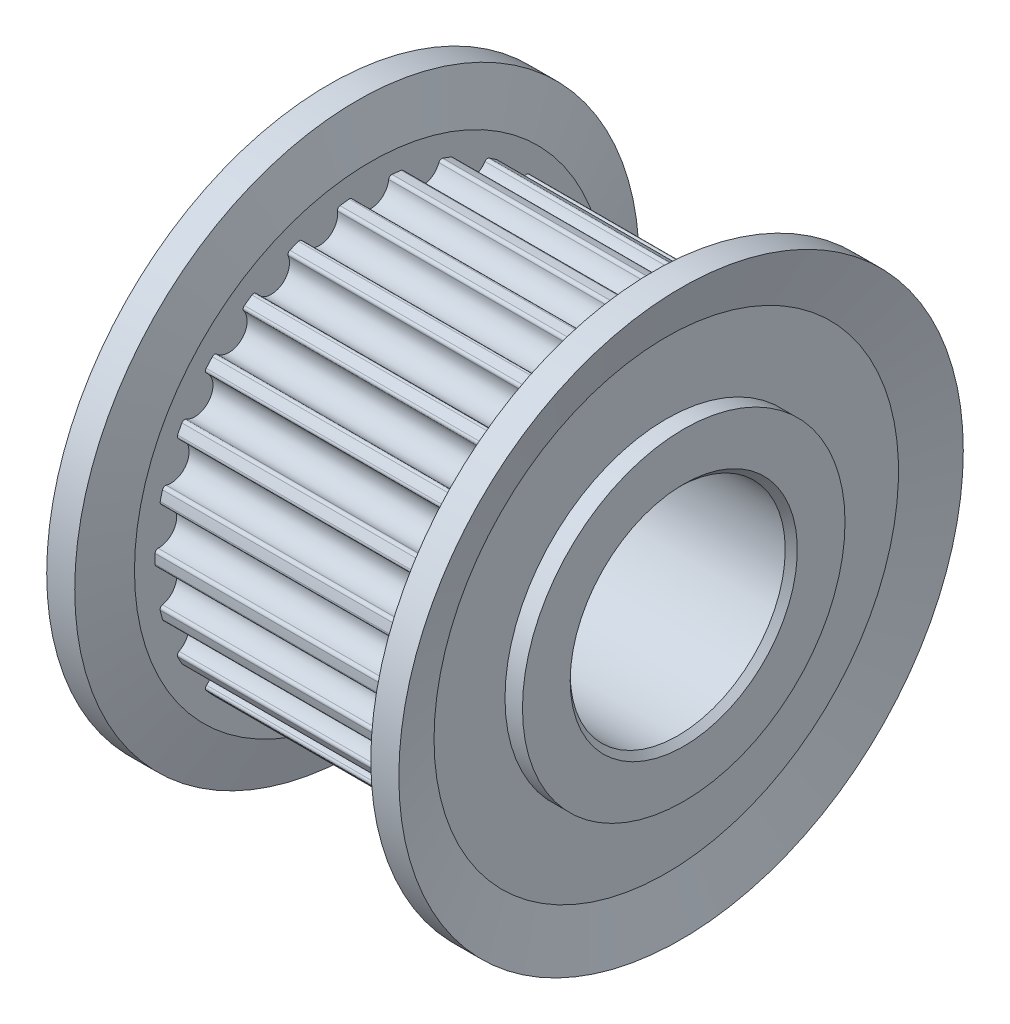
SolidWorks part; units mm, degrees
ref_plane "Front Plane" through (0, 0, 0) normal (0, 0, 1) x (1, 0, 0)
ref_plane "Top Plane" through (0, 0, 0) normal (0, 1, 0) x (1, 0, 0)
ref_plane "Right Plane" through (0, 0, 0) normal (1, 0, 0) x (0, 0, -1)
sketch "Sketch1" plane through (0, 0, 0) normal (0, 0, 1) x (1, 0, 0)
  line L0 (0, 5.27) -> (0, 10.275) construction
  line L1 (0, 0) -> (6.4763, 0) construction
  line L2 (19.85, 6) -> (19.85, 4.225)
  line L3 (33.15, 4.225) -> (33.15, 6)
  line L4 (26.5, 0) -> (26.5, 10.275) construction
  line L5 (31.5, 8.02) -> (31.5, 8.7848)
  line L6 (21.5, 8.02) -> (21.5, 8.7848)
  line L43 (20.075, 4) -> (32.925, 4)
  line L44 (21.5, 8.275) -> (31.5, 8.275) construction
  line L45 (17.85, 0) -> (35.15, 0) construction
  line L47 (21.5, 7.27) -> (31.5, 7.27) construction
  line L48 (21.5, 8.02) -> (31.5, 8.02)
  line L52 (19.85, 4.225) -> (20.075, 4)
  line L53 (20.5, 8.64) -> (20.5, 6)
  line L54 (21.5, 6) -> (19.85, 6)
  line L58 (33.15, 4.225) -> (32.925, 4)
  line L59 (32.5, 8.64) -> (32.5, 6)
  line L60 (31.5, 6) -> (33.15, 6)
  line L61 (19.95, 10.5) -> (20.5, 8.64)
  line L66 (32.5, 8.64) -> (33.05, 10.5)
  line L83 (31.5, 8.02) -> (31.5, 6)
  line L84 (31.5, 8.7848) -> (32.0072, 10.5)
  line L85 (33.05, 10.5) -> (32.0072, 10.5)
  line L86 (21.5, 8.02) -> (21.5, 6)
  line L87 (20.9928, 10.5) -> (21.5, 8.7848)
  line L88 (19.95, 10.5) -> (20.9928, 10.5)
  arc A0 (0.7949, 7.9805) -> (0.6718, 7.8795) centre (0.7838, 7.8686) ccw
  arc A1 (-0.6718, 7.8795) -> (0.6718, 7.8795) centre (0, 7.945) ccw
  arc A2 (-0.6718, 7.8795) -> (-0.7949, 7.9805) centre (-0.7838, 7.8686) ccw
  arc A3 (4.01, 6.9455) -> (0.7949, 7.9805) centre (0, 0) ccw
  arc A4 (4.1375, 7.1664) -> (-4.1375, 7.1664) centre (0, 0) ccw construction
  arc A5 (-0.7949, 7.9805) -> (-4.01, 6.9455) centre (0, 0) ccw
  dimension "D1" = 8.275
  dimension "D2" = 7.945
  dimension "D3" = 0.675
  dimension "D4" = 0.1125
  dimension "D5" = 0.225
  dimension "D6" = 0.225
  dimension "D7" = 12
  dimension "D8" = 10
  dimension "D9" = 13.3
  dimension "D10" = 16.04
  dimension "D11" = 21
  dimension "D12" = 1
  dimension "D13" = 1
  dimension "D14" = 17.28
  dimension "D15" = 17.5695
  dimension "D16" = 8
  dimension "D17" = 1.5676
  dimension "D18" = 7.8686
  dimension "D19" = 26.5
revolve "Revolve1" add sketch "Sketch1" angle 360 about L45 region at (26.5, 5.8695, 0)
sketch "Sketch5" plane through (21.5, 0, -21.5) normal (-1, 0, 0) x (0, 0, 1)
  line L1 (19, 7.6204) -> (19, 7.8883)
  line L2 (21.5, 0) -> (21.5, 19.8172) construction
  line L3 (21.5, 0) -> (2.0173, 0) construction
  line L4 (24, 7.6204) -> (24, 7.8883)
  arc A6 (22.2949, 7.9805) -> (22.1718, 7.8795) centre (22.2838, 7.8686) ccw
  arc A7 (20.8282, 7.8795) -> (22.1718, 7.8795) centre (21.5, 7.945) ccw
  arc A8 (20.8282, 7.8795) -> (20.7051, 7.9805) centre (20.7162, 7.8686) ccw
  arc A9 (24, 7.6204) -> (22.2949, 7.9805) centre (21.5, 0) ccw
  arc A10 (24, 7.8883) -> (19, 7.8883) centre (21.5, 0) ccw
  arc A11 (20.7051, 7.9805) -> (19, 7.6204) centre (21.5, 0) ccw
  circle A12 centre (21.5, 0) radius 8.02 construction
  dimension "D2" = 8.275
  dimension "D3" = 5
  dimension "D5" = 0.675
  dimension "D6" = 0.1125
  dimension "D10" = 8.02
  dimension "D7" = 1.5676
  dimension "D8" = 7.945
  dimension "D9" = 7.8686
extrude "Cut-Extrude1" cut sketch "Sketch5" against normal through all
pattern_circular "CirPattern1" count 26 over 360 about axis through (17.85, 0, 0) along (-1, 0, 0) of "Cut-Extrude1"
revolve "Revolve2" add sketch "Sketch1<4>" angle 360 about L45 region at (20.8922, 8.2727, 0) region at (32.1078, 8.2727, 0)
sketch "Sketch1<4>" plane through (0, 0, 0) normal (0, 0, 1) x (1, 0, 0) same geometry as "Sketch1"
